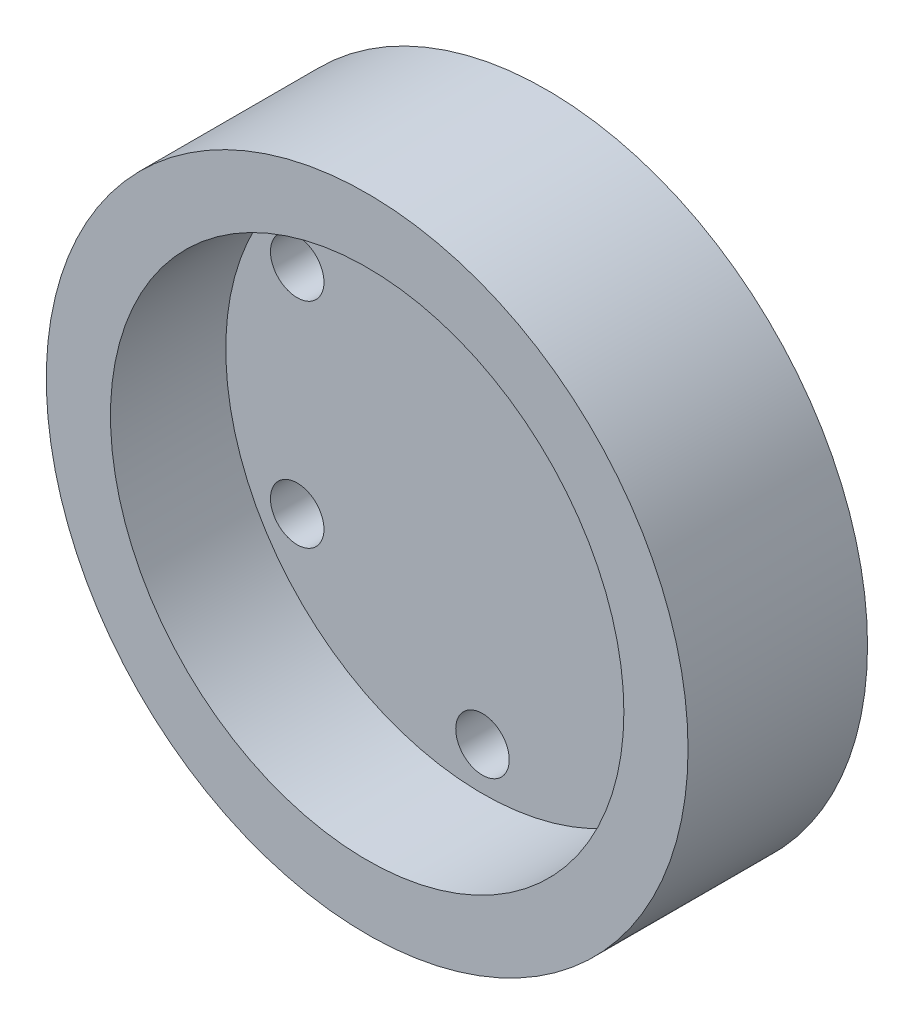
SolidWorks part; units mm, degrees
ref_plane "Front Plane" through (0, 0, 0) normal (0, 0, 1) x (1, 0, 0)
ref_plane "Top Plane" through (0, 0, 0) normal (0, 1, 0) x (1, 0, 0)
ref_plane "Right Plane" through (0, 0, 0) normal (1, 0, 0) x (0, 0, -1)
sketch "Sketch2" plane through (0, 0, 0) normal (0, 0, 1) x (1, 0, 0)
  circle A0 centre (0, 0) radius 15
  dimension "D1" = 30
extrude "Boss-Extrude1" add sketch "Sketch2" along normal blind 8.39
shell "Shell1" thickness 3 removed face at (15, 0, 8.39)
sketch "Sketch3" plane through (0, 0, 0) normal (0, 0, -1) x (-1, 0, 0)
  circle A0 centre (0, 10) radius 1.25
  circle A1 centre (0, 0) radius 15 construction
  circle A2 centre (8.6603, 5) radius 1.25
  circle A3 centre (8.6603, -5) radius 1.25
  circle A4 centre (0, -10) radius 1.25
  circle A5 centre (-8.6603, -5) radius 1.25
  circle A6 centre (-8.6603, 5) radius 1.25
  point P16 (0, 0)
  dimension "D1" = 2.5
  dimension "D2" = 10
  dimension "D3" = 6
extrude "Cut-Extrude1" cut sketch "Sketch3" against normal blind 5
